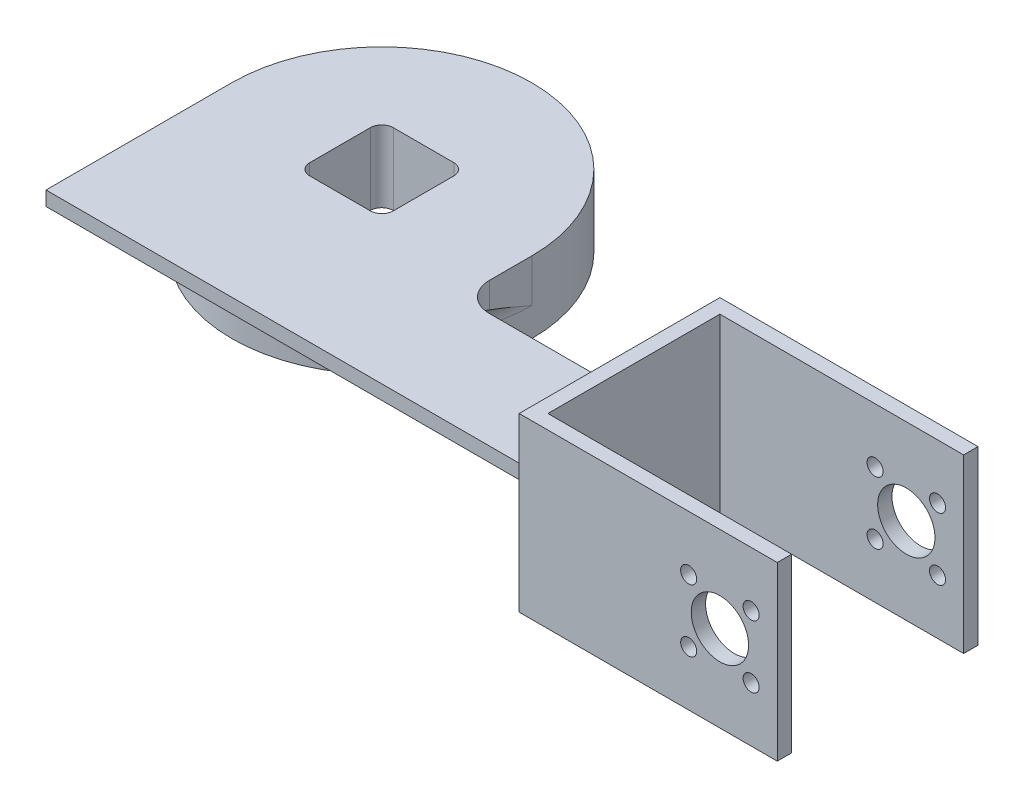
SolidWorks part; units mm, degrees
ref_plane "Front Plane" through (0, 0, 0) normal (0, 0, 1) x (1, 0, 0)
ref_plane "Top Plane" through (0, 0, 0) normal (0, 1, 0) x (1, 0, 0)
ref_plane "Right Plane" through (0, 0, 0) normal (1, 0, 0) x (0, 0, -1)
sketch "Sketch1" plane through (0, 0, 0) normal (0, 1, 0) x (1, 0, 0)
  circle A0 centre (0, 0) radius 33.2105
  dimension "D1" = 66.421
extrude "Boss-Extrude1" add sketch "Sketch1" along normal blind 15.875
sketch "Sketch2" plane through (0, 15.875, 0) normal (0, 1, 0) x (1, 0, 0)
  line L0 (0, 0) -> (-33.2105, 0) construction
  line L1 (0, 0) -> (33.2105, 0) construction
  line L2 (-33.2105, 0) -> (-33.2105, -41.148)
  line L3 (33.2105, 0) -> (33.2105, -15.748)
  line L4 (33.2105, -15.748) -> (81.0895, -15.748)
  line L5 (-33.2105, -41.148) -> (81.0895, -41.148)
  line L6 (81.0895, -15.748) -> (81.0895, -41.148)
  circle A0 centre (0, 0) radius 33.2105 construction
  circle A2 centre (0, 0) radius 33.2105
  arc A3 (-33.2105, 0) -> (33.2105, 0) centre (0, 0) ccw
  point P14 (-168.6228, -198.2806)
  dimension "D1" = 15.748
  dimension "D2" = 25.4
  dimension "D3" = 114.3
  dimension "D4" = 0
extrude "Boss-Extrude2" add sketch "Sketch2" against normal blind 3.175
fillet "Fillet1" radius 6.35 1 edges at (33.2105, 14.2875, 15.748)
fillet "Fillet2" radius 6.35 1 edges at (0, 12.7, 33.2105)
sketch "Sketch3" plane through (0, 15.875, 0) normal (0, 1, 0) x (1, 0, 0)
  line L0 (81.0895, -28.448) -> (81.0895, -50.673)
  line L1 (81.0895, -15.748) -> (81.0895, -41.148) construction
  line L2 (81.0895, -50.673) -> (138.2395, -50.673)
  line L3 (138.2395, -50.673) -> (138.2395, -47.498)
  line L4 (138.2395, -47.498) -> (84.2645, -47.498)
  line L5 (84.2645, -47.498) -> (84.2645, -9.398)
  line L6 (84.2645, -9.398) -> (138.2395, -9.398)
  line L7 (138.2395, -9.398) -> (138.2395, -6.223)
  line L8 (138.2395, -6.223) -> (81.0895, -6.223)
  line L9 (81.0895, -28.448) -> (81.0895, -6.223)
  dimension "D1" = 57.15
  dimension "D2" = 38.1
  dimension "D3" = 3.175
  dimension "D4" = 3.175
extrude "Boss-Extrude3" add sketch "Sketch3" against normal mid plane 38.1
sketch "Sketch4" plane through (0, 0, 6.223) normal (0, 0, -1) x (-1, 0, 0)
  line L0 (-138.2395, 15.875) -> (-125.5395, 15.875) construction
  line L1 (-138.2395, -3.175) -> (-138.2395, 34.925) construction
  line L2 (-125.5395, 15.875) -> (-118.6247, 22.7898) construction
  line L3 (-125.5395, 15.875) -> (-118.6247, 8.9602) construction
  line L4 (-125.5395, 15.875) -> (-132.4543, 8.9602) construction
  line L5 (-125.5395, 15.875) -> (-132.4543, 22.7898) construction
  line L7 (-138.2395, -3.175) -> (-81.0895, -3.175) construction
  circle A0 centre (-125.5395, 15.875) radius 6.35
  circle A1 centre (-132.4543, 22.7898) radius 1.778
  circle A2 centre (-118.6247, 22.7898) radius 1.778
  circle A3 centre (-118.6247, 8.9602) radius 1.778
  circle A4 centre (-132.4543, 8.9602) radius 1.778
  point P17 (-172.2295, 42.6972)
  dimension "D1" = 12.7
  dimension "D2" = 12.7
  dimension "D3" = 3.556
  dimension "D4" = 19.558
  dimension "D5" = 12.1352
extrude "Cut-Extrude1" cut sketch "Sketch4" against normal up to surface (44.45 mm away) up to face at (109.6645, 15.875, 50.673)
sketch "Sketch5" plane through (0, 15.875, 0) normal (0, 1, 0) x (1, 0, 0)
  line L1 (-9.2497, 9.2497) -> (9.2497, 9.2497)
  line L2 (-9.2497, 9.2497) -> (-9.2497, -9.2497)
  line L3 (-9.2497, -9.2497) -> (9.2497, -9.2497)
  line L4 (9.2497, 9.2497) -> (9.2497, -9.2497)
  line L5 (-9.2497, 9.2497) -> (9.2497, -9.2497) construction
  line L6 (-9.2497, -9.2497) -> (9.2497, 9.2497) construction
  point P0 (0, 0)
  dimension "D1" = 26.162
extrude "Cut-Extrude2" cut sketch "Sketch5" against normal up to surface (15.875 mm away) up to face at (0, 0, 33.2105)
fillet "Fillet3" radius 2.54 1 edges at (-9.2497, 7.9375, 9.2497)
fillet "Fillet4" radius 2.54 1 edges at (-9.2497, 7.9375, -9.2497)
fillet "Fillet5" radius 2.54 1 edges at (9.2497, 7.9375, -9.2497)
fillet "Fillet6" radius 2.54 1 edges at (9.2497, 7.9375, 9.2497)
